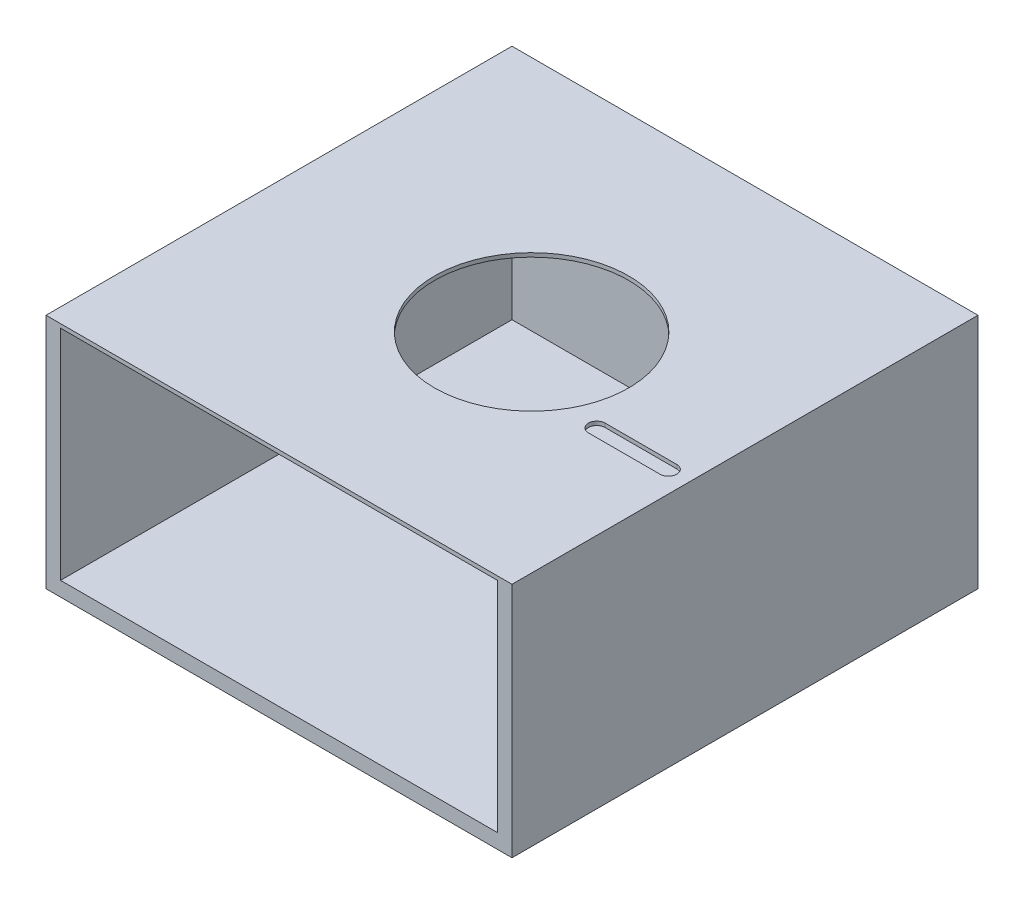
SolidWorks part; units mm, degrees
ref_plane "Front Plane" through (0, 0, 0) normal (0, 0, 1) x (1, 0, 0)
ref_plane "Top Plane" through (0, 0, 0) normal (0, 1, 0) x (1, 0, 0)
ref_plane "Right Plane" through (0, 0, 0) normal (1, 0, 0) x (0, 0, -1)
sketch "Sketch1" plane through (0, 0, 0) normal (0, 0, 1) x (1, 0, 0)
  line L1 (-152.4, -76.2) -> (152.4, -76.2)
  line L2 (-152.4, -76.2) -> (-152.4, 76.2)
  line L3 (-152.4, 76.2) -> (152.4, 76.2)
  line L4 (152.4, -76.2) -> (152.4, 76.2)
  line L5 (-152.4, -76.2) -> (152.4, 76.2) construction
  line L6 (-152.4, 76.2) -> (152.4, -76.2) construction
  point P0 (0, 0)
  dimension "D1" = 304.8
  dimension "D2" = 152.4
extrude "Boss-Extrude1" add sketch "Sketch1" along normal blind 304.8
shell "Shell1" thickness 9.525 removed face at (0, 0, 304.8) removed face at (0, 76.2, 152.4)
sketch "Sketch2" plane through (0, 76.2, 0) normal (0, 1, 0) x (1, 0, 0)
  line L0 (-142.875, -304.8) -> (142.875, -304.8)
  line L8 (-152.4, -304.8) -> (-142.875, -304.8)
  line L9 (-142.875, -304.8) -> (-142.875, -9.525)
  line L10 (-142.875, -9.525) -> (142.875, -9.525)
  line L11 (142.875, -9.525) -> (142.875, -304.8)
  line L12 (142.875, -304.8) -> (152.4, -304.8)
  line L13 (152.4, -304.8) -> (152.4, 0)
  line L14 (152.4, 0) -> (-152.4, 0)
  line L15 (-152.4, 0) -> (-152.4, -304.8)
  line L16 (-152.4, -304.8) -> (-142.875, -304.8)
  line L20 (142.875, -304.8) -> (152.4, -304.8)
  line L21 (152.4, -304.8) -> (152.4, 0)
  line L22 (152.4, 0) -> (-152.4, 0)
  line L23 (-152.4, 0) -> (-152.4, -304.8)
  dimension "D1" = 0
extrude "Boss-Extrude2" add sketch "Sketch2" along normal blind 2.54
sketch "Sketch3" plane through (0, 78.74, 0) normal (0, 1, 0) x (1, 0, 0)
  line L10 (15.875, -108.3347) -> (-28.9142, -140.876)
  line L11 (-28.9142, -140.876) -> (-11.8063, -193.5289)
  line L12 (-11.8063, -193.5289) -> (43.5563, -193.5289)
  line L13 (43.5563, -193.5289) -> (60.6642, -140.876)
  line L14 (60.6642, -140.876) -> (15.875, -108.3347)
  circle A1 centre (15.875, -155.4289) radius 3.175
sketch "Sketch4" plane through (0, 78.74, 0) normal (0, 1, 0) x (1, 0, 0)
  circle A0 centre (15.875, -155.4289) radius 63.5
  dimension "D1" = 127
extrude "Cut-Extrude1" cut sketch "Sketch4" against normal blind 7.62
sketch "Sketch5" plane through (0, 78.74, 0) normal (0, 1, 0) x (1, 0, 0)
  line L2 (89.7396, -162.406) -> (138.9776, -162.406)
  line L3 (138.9776, -156.056) -> (89.7396, -156.056)
  ellipse E1 centre (138.9776, -159.231) end of major axis (138.9776, -156.056) minor radius 3.0047
sketch "Sketch6" plane through (0, 78.74, 0) normal (0, 1, 0) x (1, 0, 0)
  line L0 (138.9776, -159.231) -> (95.0898, -159.231) construction
  line L1 (138.9776, -163.5234) -> (95.0898, -163.5234)
  line L2 (138.9776, -154.9386) -> (95.0898, -154.9386)
  arc A0 (138.9776, -163.5234) -> (138.9776, -154.9386) centre (138.9776, -159.231) ccw
  arc A1 (95.0898, -154.9386) -> (95.0898, -163.5234) centre (95.0898, -159.231) ccw
  point P3 (117.0337, -159.231)
extrude "Cut-Extrude2" [suppressed] cut sketch "Sketch6" against normal blind 2.54
sketch "Sketch8" plane through (0, 78.74, 0) normal (0, 1, 0) x (1, 0, 0)
  line L1 (138.4375, -185.3651) -> (89.5629, -185.3651)
  line L4 (-152.4, 0) -> (-152.4, -304.8)
  line L5 (-152.4, -304.8) -> (152.4, -304.8)
  line L6 (152.4, -304.8) -> (152.4, 0)
  line L7 (152.4, 0) -> (-152.4, 0)
  line L8 (-152.4, 0) -> (-152.4, -304.8)
  line L9 (-152.4, -304.8) -> (152.4, -304.8)
  line L10 (152.4, -304.8) -> (152.4, 0)
  line L11 (152.4, 0) -> (-152.4, 0)
  ellipse E2 centre (138.4375, -188.5401) end of major axis (138.4375, -185.3651) minor radius 3.0073
  dimension "D1" = 0
sketch "Sketch9" plane through (0, 78.74, 0) normal (0, 1, 0) x (1, 0, 0)
  line L0 (138.4375, -188.5401) -> (91.5808, -188.5401) construction
  line L1 (138.4375, -194.05) -> (91.5808, -194.05)
  line L2 (138.4375, -183.0302) -> (91.5808, -183.0302)
  arc A0 (138.4375, -194.05) -> (138.4375, -183.0302) centre (138.4375, -188.5401) ccw
  arc A1 (91.5808, -183.0302) -> (91.5808, -194.05) centre (91.5808, -188.5401) ccw
  point P3 (115.0091, -188.5401)
extrude "Cut-Extrude3" cut sketch "Sketch9" against normal blind 2.54
